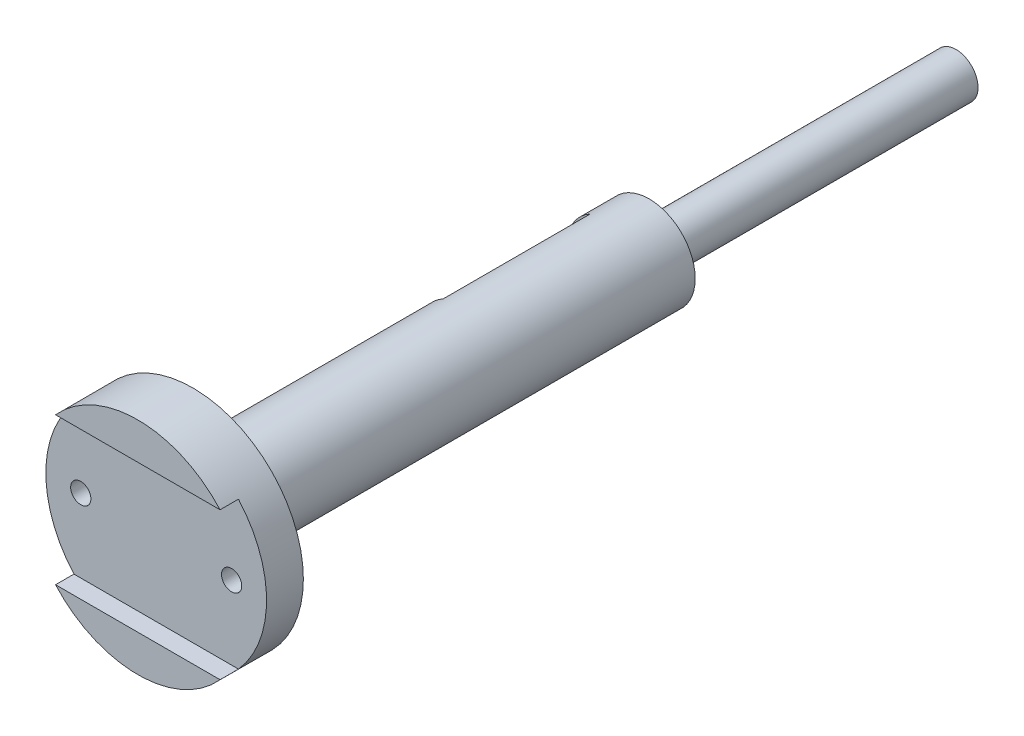
SolidWorks part; units mm, degrees
ref_plane "Plan de face" through (0, 0, 0) normal (0, 0, 1) x (1, 0, 0)
ref_plane "Plan de dessus" through (0, 0, 0) normal (0, 1, 0) x (1, 0, 0)
ref_plane "Plan de droite" through (0, 0, 0) normal (1, 0, 0) x (0, 0, -1)
sketch "Esquisse1" plane through (0, 0, 0) normal (0, 0, 1) x (1, 0, 0)
  circle A0 centre (0, 0) radius 30
  dimension "D1" = 60
extrude "Boss.-Extru.1" add sketch "Esquisse1" along normal blind 15
sketch "Esquisse2" plane through (0, 0, 0) normal (0, 0, -1) x (-1, 0, 0)
  circle A0 centre (0, 0) radius 12.5
  dimension "D1" = 25
extrude "Boss.-Extru.2" add sketch "Esquisse2" along normal blind 124
sketch "Esquisse4" plane through (0, 0, 15) normal (0, 0, 1) x (1, 0, 0)
  line L1 (115, 20) -> (-115, 20)
  line L2 (115, 20) -> (115, -20)
  line L3 (115, -20) -> (-115, -20)
  line L4 (-115, 20) -> (-115, -20)
  line L5 (115, 20) -> (-115, -20) construction
  line L6 (115, -20) -> (-115, 20) construction
  point P0 (0, 0)
  dimension "D1" = 40
  dimension "D2" = 230
extrude "Boss.-Extru.3" [suppressed] add sketch "Esquisse4" along normal blind 5
extrude "Enlèv. mat.-Extru.1" cut sketch "Esquisse4<2>" against normal blind 5
sketch "Esquisse4<2>" plane through (0, 0, 15) normal (0, 0, 1) x (1, 0, 0) same geometry as "Esquisse4"
sketch "Esquisse6" plane through (0, 0, 0) normal (0, 0, -1) x (-1, 0, 0)
  circle A2 centre (0, 0) radius 20.5
  circle A3 centre (0, 0) radius 20.5 construction
  dimension "D1" = 8
hole_wizard "Chambrage pour vis à tête hexagonale M51" positions "Esquisse15" profile "Esquisse14" counterbore size "M5" standard "Ansi Metric" end condition through all
sketch "Esquisse15" plane through (0, 0, 0) normal (0, 0, -1) x (-1, 0, 0)
  circle A0 centre (0, 0) radius 20.5 construction
  point P0 (20.5, 0)
  point P4 (-20.5, 0)
sketch "Esquisse14" plane through (-20.5, 0, 0) normal (1, 0, 0) x (0, 1, 0)
  line L0 (0, 0) -> (0, 15)
  line L1 (0, 15) -> (2.75, 15)
  line L2 (2.75, 3.605) -> (2.75, 15)
  line L3 (2.75, 3.605) -> (2.775, 3.58)
  line L4 (2.775, 3.58) -> (6.12, 3.58)
  line L5 (6.12, 3.58) -> (6.12, 0)
  line L7 (0, 0) -> (6.12, 0)
  line L9 (-2.75, 3.605) -> (-2.775, 3.58) construction
  line L11 (0, -6.35) -> (0, 107.95) construction
  dimension "Diamètre du perçage jusqu'au prochain" = 5.5
  dimension "Profondeur du perçage jusqu'au prochain" = 15
  dimension "Diamètre du chambrage" = 12.24
  dimension "Profondeur du chambrage" = 3.58
  dimension "Diamètre du fraisage milieu" = 5.55
  dimension "Angle du fraisage milieu" = 90
sketch "Esquisse17" plane through (0, 0, -124) normal (0, 0, -1) x (-1, 0, 0)
  circle A0 centre (0, 0) radius 6
  dimension "D1" = 12
extrude "Boss.-Extru.4" add sketch "Esquisse17" along normal blind 83.38
sketch "Esquisse18" plane through (0, 0, -207.38) normal (0, 0, -1) x (-1, 0, 0)
  line L0 (6.9654, 0) -> (-3.391, 0) construction
  line L1 (-3.391, 1.5) -> (6.9654, 1.5)
  line L2 (-3.391, 1.5) -> (-3.391, -1.5)
  line L3 (-3.391, -1.5) -> (6.9654, -1.5)
  line L4 (6.9654, 1.5) -> (6.9654, -1.5)
  line L5 (-3.391, 1.5) -> (6.9654, -1.5) construction
  line L6 (-3.391, -1.5) -> (6.9654, 1.5) construction
  point P0 (-0.771, 0)
  dimension "D1" = 3
  dimension "D2" = 2.62
extrude "Enlèv. mat.-Extru.2" cut sketch "Esquisse18" against normal blind 3
sketch "Esquisse19" plane through (0, 0, -124) normal (0, 0, -1) x (-1, 0, 0)
  line L0 (6, 10.9659) -> (6, -10.9659)
  line L1 (6, 10.9659) -> (13.9334, 10.9659)
  line L2 (6, -10.9659) -> (13.9334, -10.9659)
  line L3 (13.9334, 10.9659) -> (13.9334, -10.9659)
  circle A0 centre (0, 0) radius 12.5 construction
  circle A1 centre (0, 0) radius 12.5 construction
extrude "Enlèv. mat.-Extru.3" cut sketch "Esquisse19" against normal blind 50
sketch "Esquisse21" plane through (0, 0, -124) normal (0, 0, -1) x (-1, 0, 0)
  circle A0 centre (0, 0) radius 12.5
extrude "Boss.-Extru.6" add sketch "Esquisse21" against normal blind 10
hole_wizard "Dégagement M41" positions "Esquisse23" profile "Esquisse22" hole size "M4" standard "JIS"
sketch "Esquisse23" plane through (-6, 0, 0) normal (-1, 0, 0) x (0, 0, 1)
  point P0 (-82.1, 5.8507)
  point P2 (-93.1, -2.1493)
  point P4 (-93.1, 5.8507)
  point P6 (-104.1, 5.8507)
sketch "Esquisse22" plane through (-6, 5.8507, -82.1) normal (0, 1, 0) x (0, 0, 1)
  line L0 (0, 0) -> (0, 4.299)
  line L1 (0, 4.299) -> (2.25, 3)
  line L2 (2.25, 3) -> (2.25, 0)
  line L5 (2.25, 0) -> (0, 0)
  line L10 (0, 4.299) -> (-2.25, 3) construction
  line L11 (0, -6.35) -> (0, 107.95) construction
  dimension "Diamètre du perçage" = 4.5
  dimension "Profondeur du perçage" = 3
  dimension "Angle de pointe" = 120
